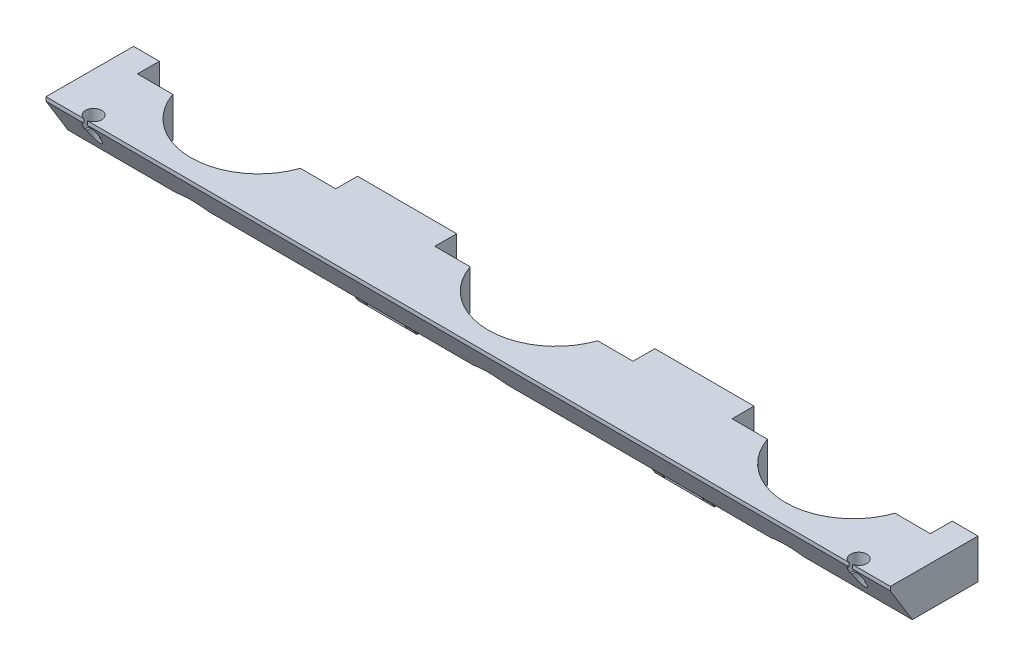
SolidWorks part; units mm, degrees
ref_plane "Płaszczyzna przednia" through (0, 0, 0) normal (0, 0, 1) x (1, 0, 0)
ref_plane "Płaszczyzna górna" through (0, 0, 0) normal (0, 1, 0) x (1, 0, 0)
ref_plane "Płaszczyzna prawa" through (0, 0, 0) normal (1, 0, 0) x (0, 0, -1)
sketch "Sketch2" plane through (0, 0, 0) normal (0, 1, 0) x (1, 0, 0)
  line L2 (-138.973, 39.1792) -> (-139.0228, 17.1793)
  line L3 (-139.0228, 17.1793) -> (73.9767, 16.6977)
  line L4 (74.027, 38.6976) -> (73.9767, 16.6977)
  line L5 (-107.4205, 62.3676) -> (-107.5199, 18.3936) construction
  line L7 (-132.4855, 33.6645) -> (-123.5712, 33.6443)
  line L9 (-132.4855, 33.6645) -> (-132.473, 39.1645)
  line L10 (-82.473, 39.0515) -> (-82.4855, 33.5515)
  line L11 (-138.973, 39.1792) -> (-132.473, 39.1645)
  line L12 (-57.4857, 33.4949) -> (-57.4732, 38.995)
  line L13 (-82.473, 39.0515) -> (-57.4732, 38.995)
  line L14 (-82.4855, 33.5515) -> (-91.3999, 33.5716)
  line L15 (-57.4857, 33.4949) -> (-48.5714, 33.4748)
  line L16 (-7.4857, 33.3819) -> (-16.4001, 33.402)
  line L17 (-7.4732, 38.8819) -> (-7.4857, 33.3819)
  line L18 (17.5141, 33.3253) -> (17.5266, 38.8254)
  line L19 (17.5141, 33.3253) -> (26.4284, 33.3052)
  line L20 (67.5141, 33.2123) -> (58.5997, 33.2325)
  line L21 (67.5266, 38.7123) -> (67.5141, 33.2123)
  line L22 (-7.4732, 38.8819) -> (17.5266, 38.8254)
  line L23 (67.5266, 38.7123) -> (74.027, 38.6976)
  arc A4 (-123.5712, 33.6443) -> (-91.3999, 33.5716) centre (-107.4731, 39.108) ccw
  arc A5 (-48.5714, 33.4748) -> (-16.4001, 33.402) centre (-32.4733, 38.9384) ccw
  arc A6 (26.4284, 33.3052) -> (58.5997, 33.2325) centre (42.5265, 38.7688) ccw
  point P4 (-104.1372, 39.0751)
  point P8 (-115.6371, 39.1103)
  point P12 (-95.973, 39.082)
  point P15 (-107.4702, 40.3806)
  dimension "D3" = 31.5
  dimension "D5" = 213
  dimension "D9" = 6.5
  dimension "D4" = 50.0001
  dimension "D14" = 34
  dimension "D11" = 17
  dimension "D1" = 213
  dimension "D2" = 22
  dimension "D6" = 360
  dimension "D7" = 13.5
  dimension "D8" = 213.0005
  dimension "D10" = 0
  dimension "D12" = 5.5
  dimension "D13" = 50
  dimension "D15" = 3
  dimension "D16" = 89.999
  dimension "D17" = 8.9143
extrude "Boss-Extrude3" add sketch "Sketch2" along normal blind 10
sketch "Sketch4" plane through (0.0879, 0, -38.8648) normal (0.0023, 0, -1) x (-1, 0, -0.0023)
  line L0 (62.5612, -12) -> (77.5612, -12)
  line L1 (62.5612, -12) -> (70.0612, -8.5) construction
  line L2 (57.5613, 0) -> (82.5611, 0) construction
  line L3 (77.5612, -12) -> (82.5611, 0)
  line L4 (62.5612, -12) -> (57.5613, 0)
  line L5 (77.5612, -12) -> (70.0612, -8.5) construction
  circle A0 centre (70.0612, -8.5) radius 1.5
  line M8 (57.5613, 0) -> (82.5611, 0)
  dimension "D3" = 3
  dimension "D1" = 15
  dimension "D2" = 12
  dimension "D4" = 3.5
extrude "Boss-Extrude4" add sketch "Sketch4" against normal blind 5 contours L4 L0 L3 A0 M8
ref_plane "Plane1" through (-77.561, 0, -0.1754) normal (1, 0, 0.0023) x (0.0023, 0, -1)
sketch "Sketch5" plane through (-77.561, 0, -0.1754) normal (1, 0, 0.0023) x (0.0023, 0, -1)
  line L0 (33.8649, -12) -> (26.8649, 0)
  line L5 (33.3649, 0) -> (33.8649, 0) construction
rib "Rib6" sketch "Sketch5" sketch "Sketch5" thickness 2.5 parameters "D1"=2.5
ref_plane "Plane3" through (-70.061, 0, -0.1584) normal (1, 0, 0.0023) x (0.0023, 0, -1)
mirror "Mirror2" about plane through (-70.061, 0, -0.1584) normal (1, 0, 0.0023) of "Rib6"
chamfer "Chamfer2" distance 1 angle 45 1 edges at (-71.4844, -8.5, -34.0266)
chamfer "Chamfer3" distance 5.5 distance2 9 1 edges at (-32.523, 0, -16.9385)
pattern_linear "LPattern4" count 2 spacing 75 along (1, 0, 0.0023) of "Boss-Extrude4", "Rib6", "Mirror2", "Chamfer2"
sketch "Sketch8" plane through (0, 10, 0) normal (0, 1, 0) x (1, 0, 0)
  line L0 (-138.973, 39.1792) -> (-139.0182, 19.1792)
  line L1 (-139.0182, 19.1792) -> (-129.0182, 19.1566)
  line L2 (-138.973, 39.1792) -> (-139.0228, 17.1793) construction
  circle A0 centre (-129.0182, 19.1566) radius 2.05
  dimension "D3" = 4.1
  dimension "D1" = 20
  dimension "D2" = 10
extrude "Cut-Extrude1" cut sketch "Sketch8" against normal blind 4
sketch "Sketch9" plane through (0, 6, 0) normal (0, 1, 0) x (1, 0, 0)
  circle A0 centre (-129.0182, 19.1566) radius 1.6
  circle A2 centre (-129.0182, 19.1566) radius 2.05 construction
  dimension "D1" = 3.2
extrude "Cut-Extrude2" cut sketch "Sketch9" against normal blind 5
ref_plane "Plane4" through (-32.5612, 0, -0.0736) normal (-1, 0, -0.0023) x (-0.0023, 0, 1)
mirror "Mirror4" about plane through (-32.5612, 0, -0.0736) normal (-1, 0, -0.0023) of "Cut-Extrude2", "Cut-Extrude1"
